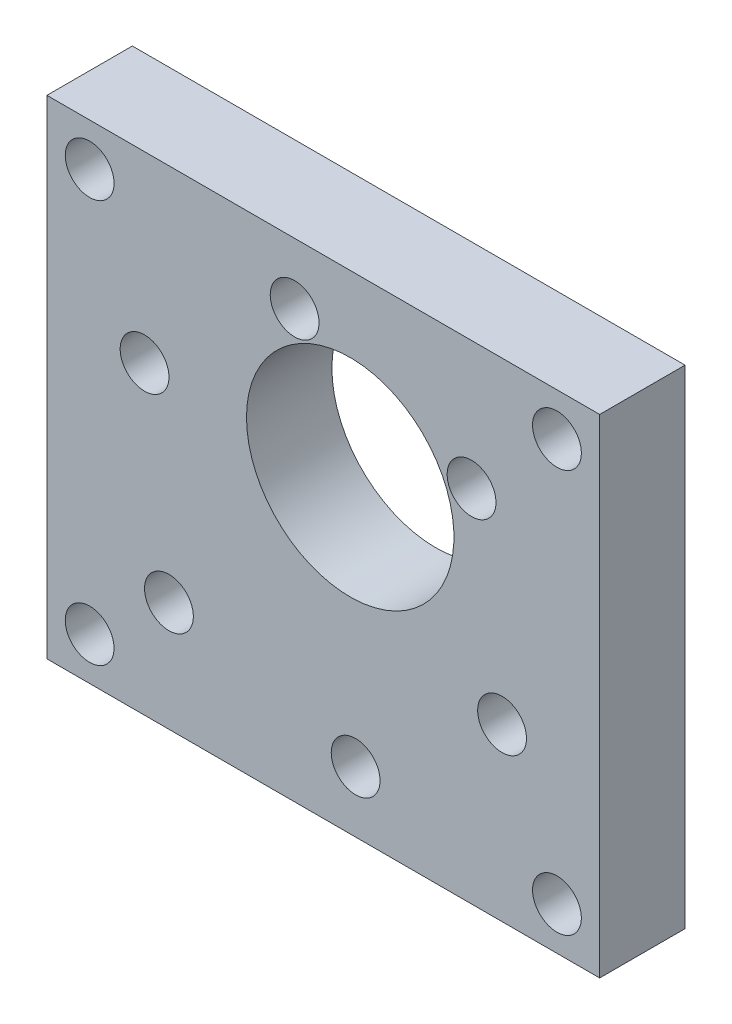
SolidWorks part; units mm, degrees
ref_plane "Plan de face" through (0, 0, 0) normal (0, 0, 1) x (1, 0, 0)
ref_plane "Plan de dessus" through (0, 0, 0) normal (0, 1, 0) x (1, 0, 0)
ref_plane "Plan de droite" through (0, 0, 0) normal (1, 0, 0) x (0, 0, -1)
sketch "Esquisse1" plane through (0, 0, 0) normal (0, 0, 1) x (1, 0, 0)
  line L1 (-19.1726, 20.5454) -> (26.1274, 20.5454)
  line L2 (-19.1726, 20.5454) -> (-19.1726, -19.4546)
  line L3 (-19.1726, -19.4546) -> (26.1274, -19.4546)
  line L4 (26.1274, 20.5454) -> (26.1274, -19.4546)
  dimension "D1" = 45.3
  dimension "D2" = 40
extrude "Boss.-Extru.1" add sketch "Esquisse1" against normal blind 7
hole_wizard "Chambrage pour vis à six pans creux M42" positions "Esquisse4" profile "Esquisse5" counterbore size "M4" standard "ISO" end condition up to next
sketch "Esquisse4" plane through (0, 0, -7) normal (0, 0, -1) x (-1, 0, 0)
  line L0 (-26.1274, 20.5454) -> (19.1726, 20.5454) construction
  line L1 (-26.1274, -19.4546) -> (-26.1274, 20.5454) construction
  line L2 (19.1726, 20.5454) -> (19.1726, -19.4546) construction
  line L3 (19.1726, -19.4546) -> (-26.1274, -19.4546) construction
  point P0 (-22.6274, 17.0454)
  point P7 (15.6726, 17.0454)
  point P12 (15.6726, -15.9546)
  point P17 (-22.6274, -15.9546)
  dimension "D1" = 3.5
  dimension "D2" = 3.5
  dimension "D3" = 3.5
  dimension "D4" = 3.5
sketch "Esquisse5" plane through (22.6274, 17.0454, -7) normal (1, 0, 0) x (0, 1, 0)
  line L0 (0, 0) -> (0, 7)
  line L1 (0, 7) -> (2, 7)
  line L3 (2, 7) -> (2, 3)
  line L4 (2, 3) -> (3, 3)
  line L5 (3, 3) -> (3, 0)
  line L7 (3, 0) -> (0, 0)
  line L11 (0, -6.35) -> (0, 107.95) construction
  dimension "Diamètre du perçage jusqu'au prochain" = 4
  dimension "Profondeur du perçage jusqu'au prochain" = 7
  dimension "Diamètre du chambrage" = 6
  dimension "Profondeur du chambrage" = 3
hole_wizard "Chambrage pour vis à six pans creux M43" positions "Esquisse6" profile "Esquisse7" counterbore size "M4" standard "ISO" end condition up to next
sketch "Esquisse6" plane through (0, 0, -7) normal (0, 0, -1) x (-1, 0, 0)
  point P0 (-18.1274, -5.4546)
  point P7 (-1.1274, 15.5454)
  point P12 (11.1726, 5.5454)
  point P14 (9.1726, -10.4546)
  point P16 (-15.6274, 10.0454)
  point P18 (-6.1274, -14.4546)
sketch "Esquisse7" plane through (18.1274, -5.4546, -7) normal (1, 0, 0) x (0, 1, 0)
  line L0 (0, 0) -> (0, 7)
  line L1 (0, 7) -> (2, 7)
  line L3 (2, 7) -> (2, 3)
  line L4 (2, 3) -> (3, 3)
  line L5 (3, 3) -> (3, 0)
  line L7 (3, 0) -> (0, 0)
  line L11 (0, -6.35) -> (0, 107.95) construction
  dimension "Diamètre du perçage jusqu'au prochain" = 4
  dimension "Profondeur du perçage jusqu'au prochain" = 7
  dimension "Diamètre du chambrage" = 6
  dimension "Profondeur du chambrage" = 3
sketch "Esquisse8" plane through (0, 0, -7) normal (0, 0, -1) x (-1, 0, 0)
  circle A0 centre (-5.683, 5.8664) radius 8.5
  dimension "D1" = 17
extrude "Enlèv. mat.-Extru.1" cut sketch "Esquisse8" against normal blind 7 contours A0
